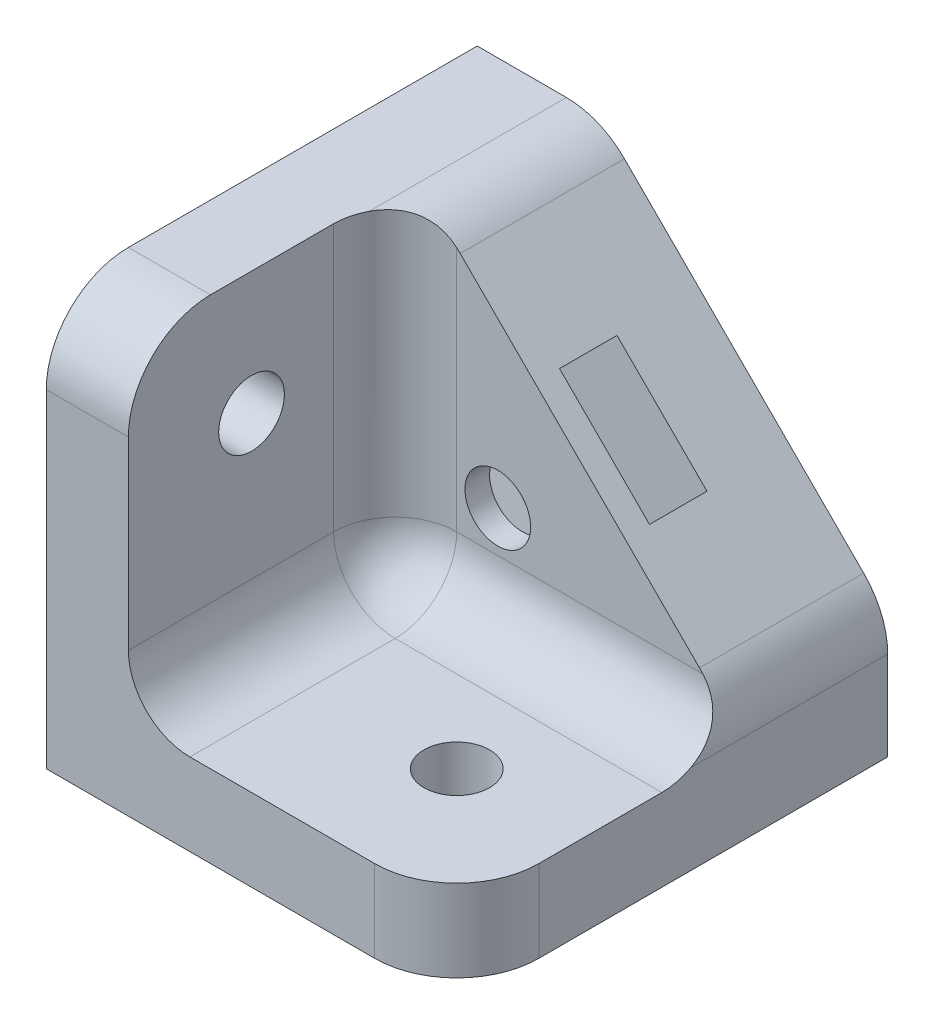
SolidWorks part; units mm, degrees
ref_plane "Front Plane" through (0, 0, 0) normal (0, 0, 1) x (1, 0, 0)
ref_plane "Top Plane" through (0, 0, 0) normal (0, 1, 0) x (1, 0, 0)
ref_plane "Right Plane" through (0, 0, 0) normal (1, 0, 0) x (0, 0, -1)
sketch "Sketch4" plane through (0, 0, 0) normal (0, 0, 1) x (1, 0, 0)
  line L2 (0, 0) -> (0, 20)
  line L3 (0, 20) -> (4, 20)
  line L4 (4, 4) -> (4, 20)
  line L5 (0, 0) -> (20, 0)
  line L7 (4, 4) -> (20, 4)
  line L8 (20, 0) -> (20, 4)
  line L9 (4, 20) -> (6, 20)
  line L10 (6, 20) -> (20, 6)
  line L11 (20, 6) -> (20, 4)
  dimension "D1" = 4
  dimension "D2" = 4
  dimension "D3" = 20
  dimension "D4" = 20
  dimension "D5" = 2
  dimension "D6" = 2
extrude "Boss-Extrude4" add sketch "Sketch4" along normal blind 8 separate body contours L5 L8 L7 L4 L3 L2 | L4 L7 region at (0.2828, 10, 0) region at (9.9325, 9.9325, 0)
extrude "Boss-Extrude5" add sketch "Sketch4<4>" along normal blind 21 contours L5 L8 L7 L4 L3 L2 region at (0.2828, 10, 0)
sketch "Sketch4<4>" plane through (0, 0, 0) normal (0, 0, 1) x (1, 0, 0) same geometry as "Sketch4"
sketch "Sketch5" plane through (13, 13, 0) normal (0.7071, 0.7071, 0) x (0, 0, -1)
  line L1 (-6.8, -3.1) -> (-4, -3.1)
  line L2 (-6.8, -3.1) -> (-6.8, 3.1)
  line L3 (-6.8, 3.1) -> (-4, 3.1)
  line L4 (-4, -3.1) -> (-4, 3.1)
  line L5 (-6.8, -3.1) -> (-4, 3.1) construction
  line L6 (-6.8, 3.1) -> (-4, -3.1) construction
  line L8 (0, 9.8995) -> (0, -9.8995) construction
  point P0 (-5.4, 0)
  dimension "D1" = 2.8
  dimension "D2" = 4
  dimension "D3" = 6.2
extrude "Cut-Extrude1" cut sketch "Sketch5" against normal blind 9
hole_wizard "Ø3.2 (3.2) Diameter Hole1" positions "3DSketch2" profile "Sketch6" hole size "Ø3.2" standard "ANSI Metric" end condition through all
sketch3d "3DSketch2"
  line L0 (0, 0, 21) -> (0, 0, 0) construction
  line L1 (0, 0, 0) -> (20, 0, 0) construction
  line L2 (0, 0, 0) -> (0, 20, 0) construction
  point P0 (14, 0, 15)
  point P2 (0, 14, 15)
  point P4 (9, 9, 0)
  dimension "D1" = 14
  dimension "D2" = 14
  dimension "D3" = 15
  dimension "D4" = 15
  dimension "D5" = 9
  dimension "D6" = 9
sketch "Sketch6" plane through (14, 0, 15) normal (1, 0, 0) x (0, 0, -1)
  line L0 (0, 0) -> (0, 20)
  line L1 (0, 20) -> (1.6, 20)
  line L2 (1.6, 20) -> (1.6, 0)
  line L5 (1.6, 0) -> (0, 0)
  line L11 (0, -6.35) -> (0, 107.95) construction
  dimension "Thru Hole Dia." = 3.2
  dimension "Thru Hole Depth" = 20
chamfer "Chamfer1" distance 1.5 angle 45 2 edges at (4.444, 8.8281, 5.4) (8.8281, 4.444, 5.4)
fillet "Fillet1" radius 3 3 edges at (12, 4, 8) (4, 4, 14.5) (4, 12, 8)
fillet "Fillet2" radius 4 4 edges at (6, 20, 4.0858) (20, 6, 4.0858) (20, 2, 21) (2, 20, 21)
equation "\"D2@Sketch4\"=\"D1@Sketch4\""
equation "\"D4@Sketch4\"=\"D3@Sketch4\""
equation "\"D6@Sketch4\"=\"D5@Sketch4\""
